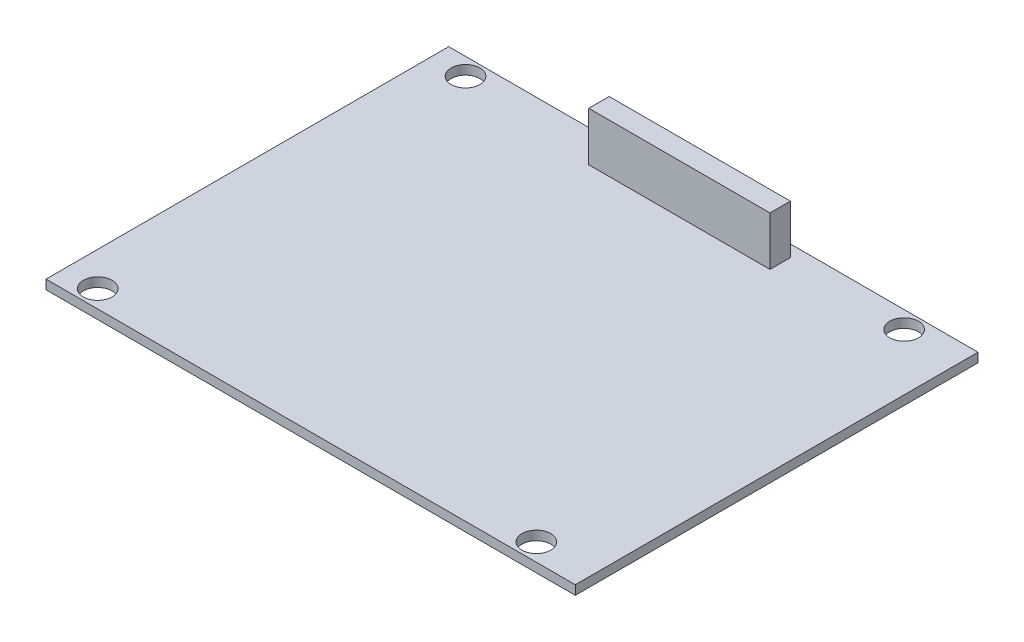
SolidWorks part; units mm, degrees
ref_plane "Front Plane" through (0, 0, 0) normal (0, 0, 1) x (1, 0, 0)
ref_plane "Top Plane" through (0, 0, 0) normal (0, 1, 0) x (1, 0, 0)
ref_plane "Right Plane" through (0, 0, 0) normal (1, 0, 0) x (0, 0, -1)
sketch "Sketch1" plane through (0, 0, 0) normal (0, 1, 0) x (1, 0, 0)
  line L1 (0, 0) -> (92, 0)
  line L2 (0, 0) -> (0, 70)
  line L3 (0, 70) -> (92, 70)
  line L4 (92, 0) -> (92, 70)
  circle A0 centre (5.92, 3.07) radius 2.5
  circle A1 centre (82.16, 3.07) radius 2.5
  circle A2 centre (82.16, 67) radius 2.5
  circle A3 centre (5.92, 67) radius 2.5
  dimension "D5" = 9.84
  dimension "D7" = 9.84
  dimension "D9" = 3
  dimension "D1" = 92
  dimension "D2" = 70
  dimension "D3" = 5.92
  dimension "D4" = 3.07
  dimension "D6" = 3.07
  dimension "D8" = 3
  dimension "D10" = 5.92
extrude "Y+ PCB extr" add sketch "Sketch1" along normal blind 1.6
sketch "Sketch2" plane through (0, 1.6, 0) normal (0, 1, 0) x (1, 0, 0)
  line L0 (92, 70) -> (0, 70) construction
  line L1 (29.95, 67.94) -> (61.45, 67.94)
  line L2 (29.95, 67.94) -> (29.95, 64.39)
  line L3 (29.95, 64.39) -> (61.45, 64.39)
  line L4 (61.45, 67.94) -> (61.45, 64.39)
  line L5 (0, 70) -> (0, 0) construction
  dimension "D1" = 2.06
  dimension "D2" = 29.95
  dimension "D3" = 31.5
  dimension "D4" = 3.55
extrude "Boss-Extrude2" add sketch "Sketch2" along normal blind 8.5
